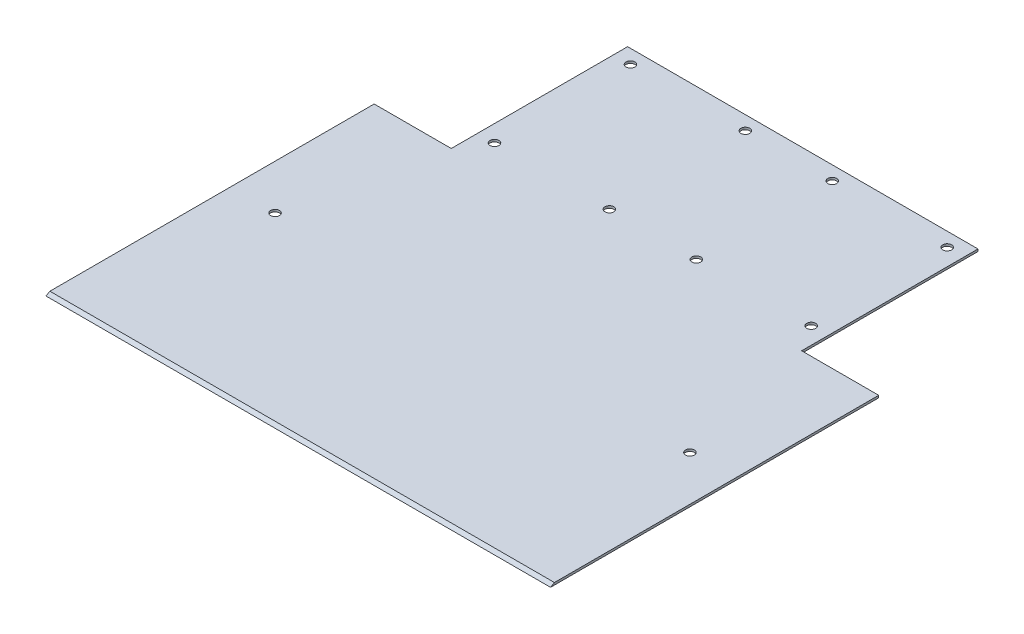
SolidWorks part; units mm, degrees
ref_plane "Alzado" through (0, 0, 0) normal (0, 0, 1) x (1, 0, 0)
ref_plane "Planta" through (0, 0, 0) normal (0, 1, 0) x (1, 0, 0)
ref_plane "Vista lateral" through (0, 0, 0) normal (1, 0, 0) x (0, 0, -1)
sketch "Croquis1" plane through (0, 0, 0) normal (0, 1, 0) x (1, 0, 0)
  line L0 (-62.5, 90) -> (-62.5, 27.08)
  line L1 (90, -90) -> (-90, -90)
  line L2 (90, -90) -> (90, 27.08)
  line L3 (62.5, 90) -> (-62.5, 90)
  line L4 (-90, -90) -> (-90, 27.08)
  line L5 (90, -90) -> (-62.5, 62.5) construction
  line L6 (62.5, 62.5) -> (-90, -90) construction
  line L7 (-62.5, 27.08) -> (-90, 27.08)
  line L8 (0, 90) -> (0, -90) construction
  line L9 (62.5, 27.08) -> (90, 27.08)
  line L10 (62.5, 90) -> (62.5, 27.08)
  point P0 (0, 0)
  dimension "D1" = 125
  dimension "D2" = 180
  dimension "D3" = 27.5
  dimension "D4" = 62.92
  dimension "D5" = 27.5
extrude "Saliente-Extruir1" add sketch "Croquis1" along normal blind 0.8
sketch "Croquis2" plane through (-90, 0, 0) normal (-1, 0, 0) x (0, 0, 1)
  line L0 (90, 0) -> (88.6144, 0.8)
  line L1 (-27.08, 0.8) -> (90, 0.8) construction
  line L2 (88.6144, 0.8) -> (90, 0.8)
  line L3 (90, 0.8) -> (90, 0)
  dimension "D1" = 60
extrude "Cortar-Extruir1" cut sketch "Croquis2" against normal up to next
sketch "Croquis3" plane through (0, 0.8, 0) normal (0, 1, 0) x (1, 0, 0)
  circle A0 centre (74, -24.2793) radius 1.585
extrude "Cortar-Extruir2" cut sketch "Croquis3" against normal up to next
mirror "Simetría1" about plane through (0, 0, 0) normal (1, 0, 0) of "Cortar-Extruir2"
sketch "Croquis4" plane through (0, 0.8, 0) normal (0, 1, 0) x (1, 0, 0)
  circle A0 centre (-56.5, 36.5056) radius 1.585
  circle A1 centre (-15.5, 36.5056) radius 1.585
  circle A2 centre (-15.5, 85.0056) radius 1.585
  circle A3 centre (-56.5, 85.0056) radius 1.585
extrude "Cortar-Extruir3" cut sketch "Croquis4" against normal up to next
sketch "Croquis6" plane through (0, 0.8, 0) normal (0, 1, 0) x (1, 0, 0)
  circle A0 centre (56.5, 85.0056) radius 1.585
  circle A1 centre (15.5, 85.0056) radius 1.585
  circle A2 centre (15.5, 36.5056) radius 1.585
  circle A3 centre (56.5, 36.5056) radius 1.585
extrude "Cortar-Extruir4" cut sketch "Croquis6" against normal up to next
